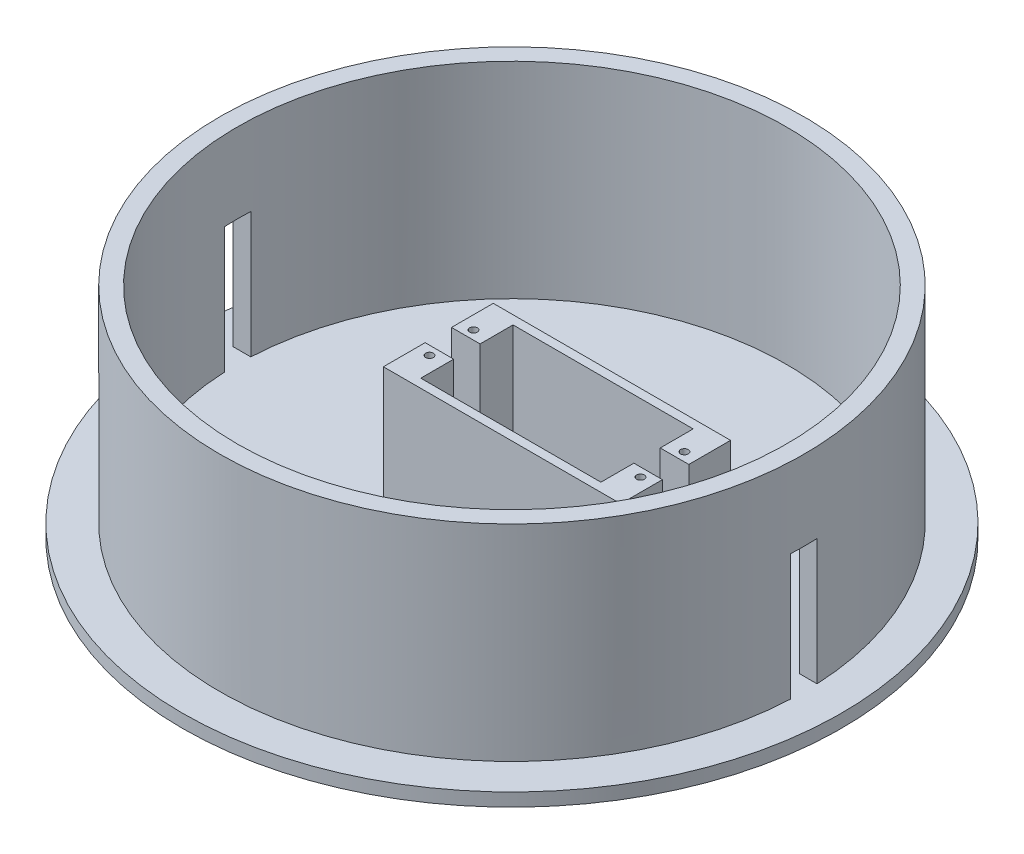
SolidWorks part; units mm, degrees
ref_plane "Front Plane" through (0, 0, 0) normal (0, 0, 1) x (1, 0, 0)
ref_plane "Top Plane" through (0, 0, 0) normal (0, 1, 0) x (1, 0, 0)
ref_plane "Right Plane" through (0, 0, 0) normal (1, 0, 0) x (0, 0, -1)
sketch "Sketch1" plane through (0, 0, 0) normal (0, 1, 0) x (1, 0, 0)
  circle A0 centre (0, 0) radius 75
  circle A1 centre (0, 0) radius 62.5
  circle A2 centre (0, 0) radius 66.5
  dimension "D1" = 150
  dimension "D2" = 125
  dimension "D3" = 4
extrude "Boss-Extrude1" add sketch "Sketch1" along normal blind 46.8 contours A2 A1 region at (-64.6191, 0, 0)
extrude "Boss-Extrude2" add sketch "Sketch1<3>" against normal blind 3 separate body contours A0 A2 region at (-72.8787, 0, 0)
sketch "Sketch1<3>" plane through (0, 0, 0) normal (0, 1, 0) x (1, 0, 0) same geometry as "Sketch1"
extrude "Boss-Extrude3" add sketch "Sketch1<5>" against normal blind 3 contours A1 | A2 A1 region at (0, 0, 0) region at (-64.6191, 0, 0)
sketch "Sketch1<5>" plane through (0, 0, 0) normal (0, 1, 0) x (1, 0, 0) same geometry as "Sketch1"
sketch "Sketch2" plane through (0, 0, 0) normal (0, 1, 0) x (1, 0, 0)
  line L1 (30.75, 10.5) -> (-10.25, 10.5)
  line L2 (30.75, 10.5) -> (30.75, -10.5)
  line L3 (30.75, -10.5) -> (-10.25, -10.5)
  line L4 (-10.25, 10.5) -> (-10.25, -10.5)
  line L7 (37.25, 12.5) -> (-16.75, 12.5)
  line L8 (37.25, 12.5) -> (37.25, -12.5)
  line L9 (37.25, -12.5) -> (-16.75, -12.5)
  line L10 (-16.75, 12.5) -> (-16.75, -12.5)
  line L13 (34.25, 5) -> (-13.75, 5)
  line L14 (34.25, 5) -> (34.25, -5)
  line L15 (34.25, -5) -> (-13.75, -5)
  line L16 (-13.75, 5) -> (-13.75, -5)
  circle A0 centre (-13.75, -5) radius 0.875
  circle A1 centre (-13.75, 5) radius 0.875
  circle A2 centre (34.25, 5) radius 0.875
  circle A3 centre (34.25, -5) radius 0.875
  circle A4 centre (0, 0) radius 62.5 construction
  point P0 (0, 0)
  point P6 (0, 0)
  point P11 (0, 0)
  point P20 (34.25, 0)
  point P21 (30.75, 0)
  point P22 (37.25, 0)
  point P23 (0, 0)
  dimension "D7" = 1.75
  dimension "D1" = 41
  dimension "D2" = 21
  dimension "D3" = 54
  dimension "D4" = 25
  dimension "D5" = 48
  dimension "D6" = 10
  dimension "D8" = 3.5
  dimension "D9" = 3
  dimension "D10" = 34.25
extrude "Boss-Extrude4" add sketch "Sketch2" along normal blind 28.65 contours L7 L10 L9 L8 A3 L15 L2 L3 L4 A0 L16 A1 L13 L1 A2 L14 | A3 L14 A2 L13 L2 L15 | A1 L16 A0 L15 L4 L13 region at (32.4509, 0, 0) region at (-11.9509, 0, 0) region at (36.6549, 0, 0)
sketch "Sketch3" plane through (-16.75, 0, 0) normal (-1, 0, 0) x (0, 0, 1)
  line L8 (0, 0) -> (0, 28.65)
  line L9 (-12.5, 0) -> (12.5, 0) construction
  line L10 (-12.5, 28.65) -> (12.5, 28.65) construction
  line L11 (0, 28.65) -> (-3, 28.65)
  line L12 (-3, 28.65) -> (-3, 0)
  line L13 (-3, 0) -> (0, 0)
  line L14 (0, 28.65) -> (3, 28.65)
  line L15 (3, 28.65) -> (3, 0)
  line L16 (3, 0) -> (0, 0)
  line M8 (-12.5, 0) -> (12.5, 0)
  line M10 (12.5, 28.65) -> (-12.5, 28.65)
  dimension "D1" = 3
  dimension "D2" = 3
extrude "Cut-Extrude1" cut sketch "Sketch3" along normal through all and the other way through all contours L15 L8 M10 M8 | L12 L8 M10 M8 region at (-16.75, 14.325, -1.5) region at (-16.75, 14.325, 1.5)
